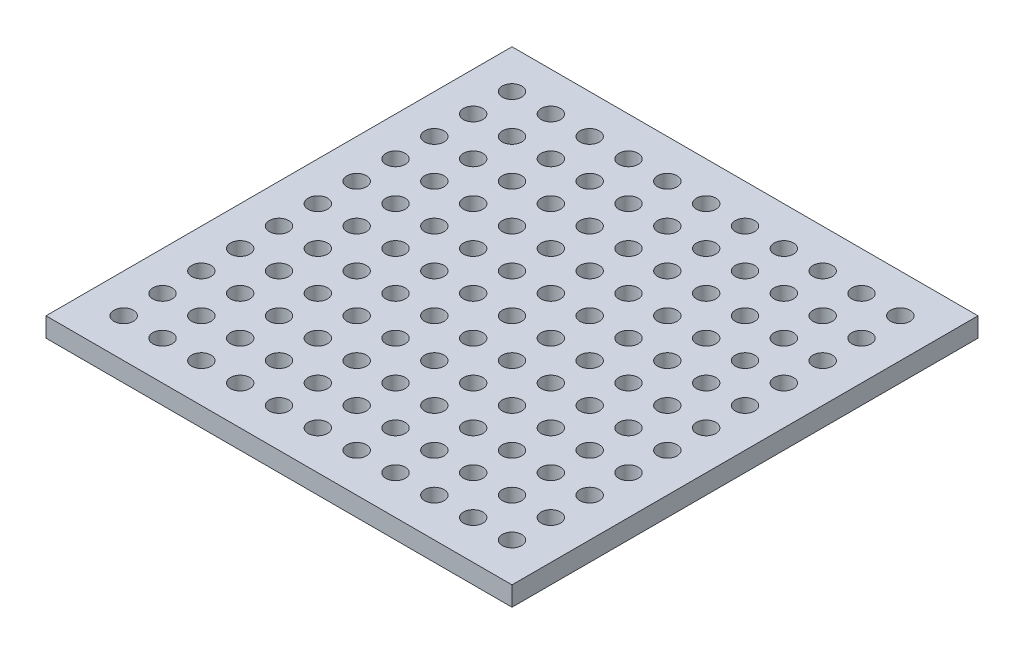
SolidWorks part; units mm, degrees
ref_plane "Front Plane" through (0, 0, 0) normal (0, 0, 1) x (1, 0, 0)
ref_plane "Top Plane" through (0, 0, 0) normal (0, 1, 0) x (1, 0, 0)
ref_plane "Right Plane" through (0, 0, 0) normal (1, 0, 0) x (0, 0, -1)
sketch "Sketch1" plane through (0, 0, 0) normal (0, 0, 1) x (1, 0, 0)
  line L1 (0, 0) -> (120, 0)
  line L2 (0, 0) -> (0, 5)
  line L3 (0, 5) -> (120, 5)
  line L4 (120, 0) -> (120, 5)
  dimension "D1" = 5
  dimension "D2" = 120
extrude "Mesh Block" add sketch "Sketch1" along normal blind 120
sketch "Sketch2" plane through (0, 5, 0) normal (0, 1, 0) x (1, 0, 0)
  line L0 (10, 0) -> (10, -10) construction
  line L1 (120, 0) -> (0, 0) construction
  line L2 (0, -120) -> (0, 0) construction
  line L3 (10, -10) -> (20, -10) construction
  line L4 (10, -10) -> (10, -20) construction
  circle A0 centre (10, -10) radius 2.5
  circle A1 centre (20, -10) radius 2.5
  circle A2 centre (30, -10) radius 2.5
  circle A3 centre (40, -10) radius 2.5
  circle A4 centre (50, -10) radius 2.5
  circle A5 centre (60, -10) radius 2.5
  circle A6 centre (70, -10) radius 2.5
  circle A7 centre (80, -10) radius 2.5
  circle A8 centre (90, -10) radius 2.5
  circle A9 centre (100, -10) radius 2.5
  circle A10 centre (110, -10) radius 2.5
  circle A12 centre (10, -20) radius 2.5
  circle A13 centre (20, -20) radius 2.5
  circle A14 centre (30, -20) radius 2.5
  circle A15 centre (40, -20) radius 2.5
  circle A16 centre (50, -20) radius 2.5
  circle A17 centre (60, -20) radius 2.5
  circle A18 centre (70, -20) radius 2.5
  circle A19 centre (80, -20) radius 2.5
  circle A20 centre (90, -20) radius 2.5
  circle A21 centre (100, -20) radius 2.5
  circle A22 centre (110, -20) radius 2.5
  circle A24 centre (10, -30) radius 2.5
  circle A25 centre (20, -30) radius 2.5
  circle A26 centre (30, -30) radius 2.5
  circle A27 centre (40, -30) radius 2.5
  circle A28 centre (50, -30) radius 2.5
  circle A29 centre (60, -30) radius 2.5
  circle A30 centre (70, -30) radius 2.5
  circle A31 centre (80, -30) radius 2.5
  circle A32 centre (90, -30) radius 2.5
  circle A33 centre (100, -30) radius 2.5
  circle A34 centre (110, -30) radius 2.5
  circle A36 centre (10, -40) radius 2.5
  circle A37 centre (20, -40) radius 2.5
  circle A38 centre (30, -40) radius 2.5
  circle A39 centre (40, -40) radius 2.5
  circle A40 centre (50, -40) radius 2.5
  circle A41 centre (60, -40) radius 2.5
  circle A42 centre (70, -40) radius 2.5
  circle A43 centre (80, -40) radius 2.5
  circle A44 centre (90, -40) radius 2.5
  circle A45 centre (100, -40) radius 2.5
  circle A46 centre (110, -40) radius 2.5
  circle A48 centre (10, -50) radius 2.5
  circle A49 centre (20, -50) radius 2.5
  circle A50 centre (30, -50) radius 2.5
  circle A51 centre (40, -50) radius 2.5
  circle A52 centre (50, -50) radius 2.5
  circle A53 centre (60, -50) radius 2.5
  circle A54 centre (70, -50) radius 2.5
  circle A55 centre (80, -50) radius 2.5
  circle A56 centre (90, -50) radius 2.5
  circle A57 centre (100, -50) radius 2.5
  circle A58 centre (110, -50) radius 2.5
  circle A60 centre (10, -60) radius 2.5
  circle A61 centre (20, -60) radius 2.5
  circle A62 centre (30, -60) radius 2.5
  circle A63 centre (40, -60) radius 2.5
  circle A64 centre (50, -60) radius 2.5
  circle A65 centre (60, -60) radius 2.5
  circle A66 centre (70, -60) radius 2.5
  circle A67 centre (80, -60) radius 2.5
  circle A68 centre (90, -60) radius 2.5
  circle A69 centre (100, -60) radius 2.5
  circle A70 centre (110, -60) radius 2.5
  circle A72 centre (10, -70) radius 2.5
  circle A73 centre (20, -70) radius 2.5
  circle A74 centre (30, -70) radius 2.5
  circle A75 centre (40, -70) radius 2.5
  circle A76 centre (50, -70) radius 2.5
  circle A77 centre (60, -70) radius 2.5
  circle A78 centre (70, -70) radius 2.5
  circle A79 centre (80, -70) radius 2.5
  circle A80 centre (90, -70) radius 2.5
  circle A81 centre (100, -70) radius 2.5
  circle A82 centre (110, -70) radius 2.5
  circle A84 centre (10, -80) radius 2.5
  circle A85 centre (20, -80) radius 2.5
  circle A86 centre (30, -80) radius 2.5
  circle A87 centre (40, -80) radius 2.5
  circle A88 centre (50, -80) radius 2.5
  circle A89 centre (60, -80) radius 2.5
  circle A90 centre (70, -80) radius 2.5
  circle A91 centre (80, -80) radius 2.5
  circle A92 centre (90, -80) radius 2.5
  circle A93 centre (100, -80) radius 2.5
  circle A94 centre (110, -80) radius 2.5
  circle A96 centre (10, -90) radius 2.5
  circle A97 centre (20, -90) radius 2.5
  circle A98 centre (30, -90) radius 2.5
  circle A99 centre (40, -90) radius 2.5
  circle A100 centre (50, -90) radius 2.5
  circle A101 centre (60, -90) radius 2.5
  circle A102 centre (70, -90) radius 2.5
  circle A103 centre (80, -90) radius 2.5
  circle A104 centre (90, -90) radius 2.5
  circle A105 centre (100, -90) radius 2.5
  circle A106 centre (110, -90) radius 2.5
  circle A108 centre (10, -100) radius 2.5
  circle A109 centre (20, -100) radius 2.5
  circle A110 centre (30, -100) radius 2.5
  circle A111 centre (40, -100) radius 2.5
  circle A112 centre (50, -100) radius 2.5
  circle A113 centre (60, -100) radius 2.5
  circle A114 centre (70, -100) radius 2.5
  circle A115 centre (80, -100) radius 2.5
  circle A116 centre (90, -100) radius 2.5
  circle A117 centre (100, -100) radius 2.5
  circle A118 centre (110, -100) radius 2.5
  circle A120 centre (10, -110) radius 2.5
  circle A121 centre (20, -110) radius 2.5
  circle A122 centre (30, -110) radius 2.5
  circle A123 centre (40, -110) radius 2.5
  circle A124 centre (50, -110) radius 2.5
  circle A125 centre (60, -110) radius 2.5
  circle A126 centre (70, -110) radius 2.5
  circle A127 centre (80, -110) radius 2.5
  circle A128 centre (90, -110) radius 2.5
  circle A129 centre (100, -110) radius 2.5
  circle A130 centre (110, -110) radius 2.5
  circle A144 centre (10, -120) radius 2.5 [skipped]
  circle A145 centre (20, -120) radius 2.5 [skipped]
  circle A146 centre (30, -120) radius 2.5 [skipped]
  circle A147 centre (40, -120) radius 2.5 [skipped]
  circle A148 centre (50, -120) radius 2.5 [skipped]
  circle A149 centre (60, -120) radius 2.5 [skipped]
  circle A150 centre (70, -120) radius 2.5 [skipped]
  circle A151 centre (80, -120) radius 2.5 [skipped]
  circle A152 centre (90, -120) radius 2.5 [skipped]
  circle A153 centre (100, -120) radius 2.5 [skipped]
  circle A154 centre (110, -120) radius 2.5 [skipped]
  circle A155 centre (120, -10) radius 2.5 [skipped]
  point P8 (0, 0)
  dimension "D1" = 5
  dimension "1" = 10
  dimension "D3" = 10
  dimension "D5" = 10
  dimension "D7" = 10
  dimension "D4" = 12
  dimension "D6" = 12
extrude "Mesh Holes" cut sketch "Sketch2" against normal through all
